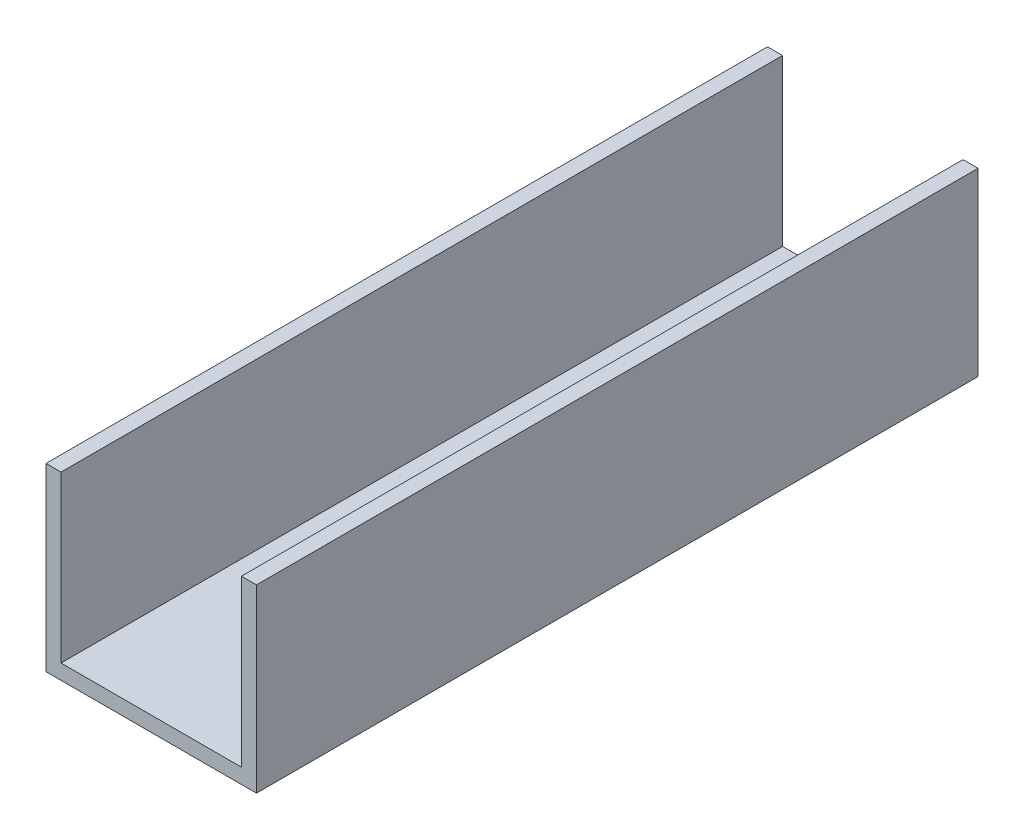
SolidWorks part; units mm, degrees
material "6063-T6"
ref_plane "Front" through (0, 0, 0) normal (0, 0, 1) x (1, 0, 0)
ref_plane "Top" through (0, 0, 0) normal (0, 1, 0) x (1, 0, 0)
ref_plane "Right" through (0, 0, 0) normal (1, 0, 0) x (0, 0, -1)
ref_axis "side-side" through (80.9, 0, 0) along (-1, 0, 0)
ref_axis "up-down" through (0, 50, 0) along (0, -1, 0)
ref_axis "front-back" through (0, 0, -80.9) along (0, 0, 1)
sketch "Sketch1" plane through (0, 0, 0) normal (0, 0, 1) x (1, 0, 0)
  line L0 (19.05, 38.1) -> (22.225, 38.1)
  line L1 (-22.225, 38.1) -> (-19.05, 38.1)
  line L2 (-22.225, 38.1) -> (-22.225, 0)
  line L3 (-22.225, 0) -> (22.225, 0)
  line L4 (22.225, 38.1) -> (22.225, 0)
  line L5 (-19.05, 3.175) -> (-19.05, 0) construction
  line L6 (-19.05, 38.1) -> (-19.05, 3.175)
  line L7 (-19.05, 3.175) -> (19.05, 3.175)
  line L8 (19.05, 38.1) -> (19.05, 3.175)
  dimension "D1" = 44.45
  dimension "D2" = 38.1
  dimension "D3" = 3.175
extrude "Boss-Extrude1" add sketch "Sketch1" against normal blind 152.4
